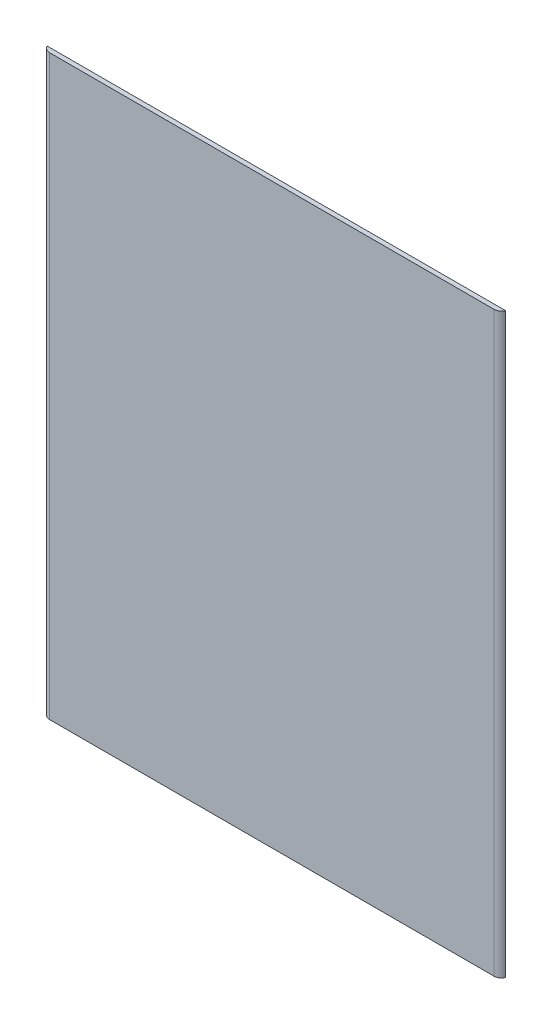
SolidWorks part; units mm, degrees
ref_plane "Plano frontal" through (0, 0, 0) normal (0, 0, 1) x (1, 0, 0)
ref_plane "Plano superior" through (0, 0, 0) normal (0, 1, 0) x (1, 0, 0)
ref_plane "Plano direito" through (0, 0, 0) normal (1, 0, 0) x (0, 0, -1)
sketch "Esboço1" plane through (0, 0, 0) normal (0, 0, 1) x (1, 0, 0)
  line L1 (0, 0) -> (600, 0)
  line L2 (0, 0) -> (0, -750)
  line L3 (0, -750) -> (600, -750)
  line L4 (600, 0) -> (600, -750)
  dimension "D1" = 600
  dimension "D2" = 750
extrude "Ressalto-extrusão3" add sketch "Esboço1" along normal blind 6
fillet "Filete4" radius 10 1 edges at (600, -375, 6)
fillet "Filete5" radius 10 1 edges at (0, -375, 6)
sketch "Esboço2" plane through (0, 0, 0) normal (0, 1, 0) x (1, 0, 0)
  line L0 (0, 0) -> (600, 0)
  line L1 (600, 0) -> (0, 0) construction
  line L2 (590.8348, -6) -> (9.1652, -6)
  line L3 (590.8348, -6) -> (9.1652, -6) construction
  line L5 (590.8348, -6) -> (172.2218, -6)
  arc A0 (590.8348, -6) -> (600, 0) centre (590.8348, 4) ccw construction
  arc A1 (0, 0) -> (9.1652, -6) centre (9.1652, 4) ccw construction
  arc A2 (0, 0) -> (9.1652, -6) centre (9.1652, 4) ccw
  arc A3 (590.8348, -6) -> (600, 0) centre (590.8348, 4) ccw
  line M3 (600, 0) -> (0, 0)
  arc M4 (0, 0) -> (9.1652, -6) centre (9.1652, 4) ccw
  line M5 (9.1652, -6) -> (590.8348, -6)
  arc M6 (590.8348, -6) -> (600, 0) centre (590.8348, 4) ccw
extrude "Ressalto-extrusão4" add sketch "Esboço2" along normal blind 6 contours L2 M6 M3 M4 M5 region at (300, 0, 2.9883)
